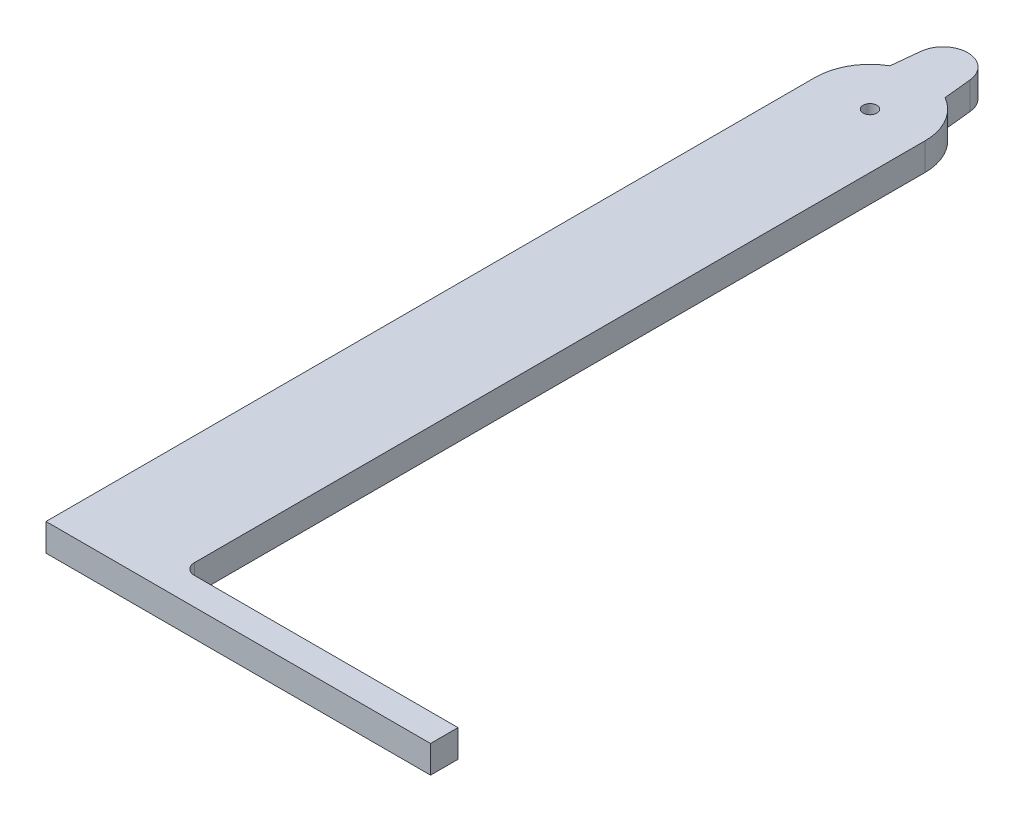
SolidWorks part; units mm, degrees
ref_plane "Front Plane" through (0, 0, 0) normal (0, 0, 1) x (1, 0, 0)
ref_plane "Top Plane" through (0, 0, 0) normal (0, 1, 0) x (1, 0, 0)
ref_plane "Right Plane" through (0, 0, 0) normal (1, 0, 0) x (0, 0, -1)
sketch "Sketch1" plane through (0, 0, 0) normal (0, 1, 0) x (1, 0, 0)
  line L1 (-12.7, 0) -> (12.7, 0)
  line L2 (-12.7, 0) -> (-12.7, -171.45)
  line L3 (-12.7, -171.45) -> (12.7, -171.45)
  line L4 (12.7, 0) -> (12.7, -171.45)
  circle A0 centre (0, 0) radius 12.7
  dimension "D1" = 25.4
  dimension "D2" = 171.45
extrude "Boss-Extrude1" add sketch "Sketch1" along normal blind 6.35 contours A0 L2 L3 L4 | L1 A0 | L1 A0 region at (0, 0, -5.39) region at (0, 0, 90.6874) region at (0, 0, 5.39)
sketch "Sketch2" plane through (0, 6.35, 0) normal (0, 1, 0) x (1, 0, 0)
  line L1 (-12.7, -171.45) -> (76.2, -171.45)
  line L2 (-12.7, -171.45) -> (-12.7, -177.8)
  line L3 (-12.7, -177.8) -> (76.2, -177.8)
  line L4 (76.2, -171.45) -> (76.2, -177.8)
  dimension "D1" = 88.9
  dimension "D2" = 6.35
extrude "Boss-Extrude2" add sketch "Sketch2" against normal up to surface (6.35 mm away) up to face at (0, 0, 82.55)
fillet "Fillet1" radius 2.54 1 edges
sketch "Sketch3" plane through (0, 0, 0) normal (0, -1, 0) x (-1, 0, 0)
  line L4 (-7.3841, 1.2138) -> (7.3841, 1.2138)
  line L6 (-7.3841, 1.2138) -> (-5.6981, 17.4684)
  line L7 (5.6981, 17.4684) -> (7.3841, 1.2138)
  line L8 (-7.3841, 1.2138) -> (-5.6981, 17.4684)
  line L9 (5.6981, 17.4684) -> (7.3841, 1.2138)
  arc A3 (5.6981, 17.4684) -> (-5.6981, 17.4684) centre (0, 16.8774) ccw
  arc A4 (5.6981, 17.4684) -> (-5.6981, 17.4684) centre (0, 16.8774) ccw
  dimension "D1" = 3.175
extrude "Boss-Extrude3" add sketch "Sketch3" against normal up to surface (6.35 mm away) up to face at (28.2277, 6.35, 110.1116)
sketch "Sketch4" plane through (0, 6.35, 0) normal (0, 1, 0) x (1, 0, 0)
  circle A0 centre (0, 0) radius 1.5875
  dimension "D1" = 3.175
extrude "Cut-Extrude1" cut sketch "Sketch4" against normal through all
